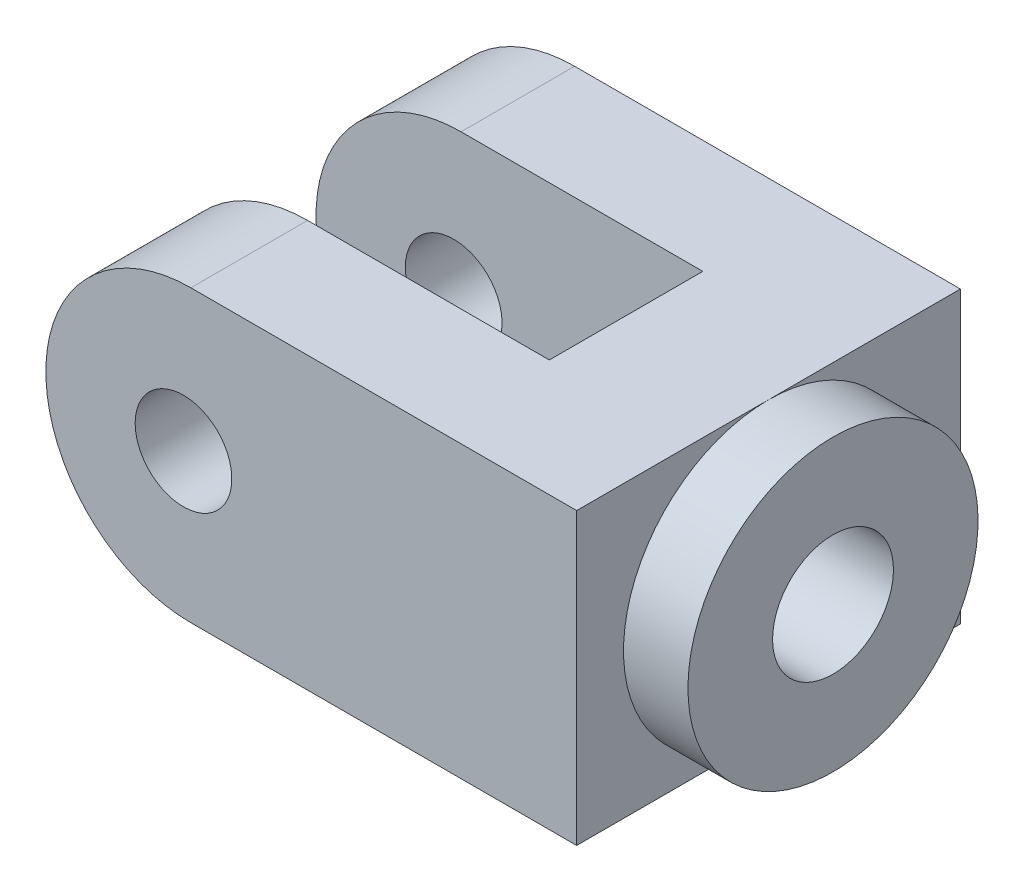
SolidWorks part; units mm, degrees
ref_plane "Front Plane" through (0, 0, 0) normal (0, 0, 1) x (1, 0, 0)
ref_plane "Top Plane" through (0, 0, 0) normal (0, 1, 0) x (1, 0, 0)
ref_plane "Right Plane" through (0, 0, 0) normal (1, 0, 0) x (0, 0, -1)
sketch "Sketch1" plane through (0, 0, 0) normal (0, 0, 1) x (1, 0, 0)
  line L1 (-66, 36) -> (66, 36)
  line L2 (-66, 36) -> (-66, -36)
  line L3 (-66, -36) -> (66, -36)
  line L4 (66, 36) -> (66, -36)
  line L5 (-66, 36) -> (66, -36) construction
  line L6 (-66, -36) -> (66, 36) construction
  point P0 (0, 0)
  dimension "D1" = 132
  dimension "D2" = 72
extrude "Boss-Extrude1" add sketch "Sketch1" along normal mid plane 95.25
sketch "Sketch2" plane through (0, 0, 47.625) normal (0, 0, 1) x (1, 0, 0)
  line L0 (66, 36) -> (-66, 36) construction
  line L1 (-66, -36) -> (66, -36) construction
  arc A0 (-29.7629, 36) -> (-29.7629, -36) centre (-29.7629, 0) ccw
  dimension "D1" = 36
  dimension "D2" = 36
extrude "Cut-Extrude1" cut sketch "Sketch2" against normal through all and the other way through all flip side to cut
sketch "Sketch3" plane through (0, -36, 0) normal (0, -1, 0) x (1, 0, 0)
  line L0 (-65.7629, -47.625) -> (-29.7629, -47.625) construction
  line L5 (-65.7629, 47.625) -> (-65.7629, -47.625) construction
  line L6 (-65.7629, 18.655) -> (30.2371, 18.655)
  line L7 (-65.7629, 18.655) -> (-65.7629, -19.445)
  line L8 (-65.7629, -19.445) -> (30.2371, -19.445)
  line L9 (30.2371, 18.655) -> (30.2371, -19.445)
  line L10 (-29.7629, 47.625) -> (-29.7629, -47.625) construction
  point P0 (0, 0)
  point P13 (-29.7629, 0)
  dimension "D1" = 38.1
  dimension "D2" = 28.18
  dimension "D3" = 60
extrude "Cut-Extrude2" cut sketch "Sketch3" against normal through all
sketch "Sketch4" plane through (66, 0, 0) normal (1, 0, 0) x (0, 0, -1)
  circle A0 centre (0, 0) radius 15
  dimension "D1" = 30
extrude "Cut-Extrude3" cut sketch "Sketch4" against normal through all
sketch "Sketch5" plane through (66, 0, 0) normal (1, 0, 0) x (0, 0, -1)
  circle A0 centre (0, 0) radius 36
  circle A1 centre (0, 0) radius 15 construction
  circle A2 centre (0, 0) radius 15
  dimension "D1" = 72
extrude "Boss-Extrude2" add sketch "Sketch5" along normal blind 16
sketch "Sketch6" plane through (0, 0, -47.625) normal (0, 0, -1) x (-1, 0, 0)
  circle A0 centre (31.5987, 0) radius 12
  dimension "D1" = 24
extrude "Cut-Extrude4" cut sketch "Sketch6" against normal through all
